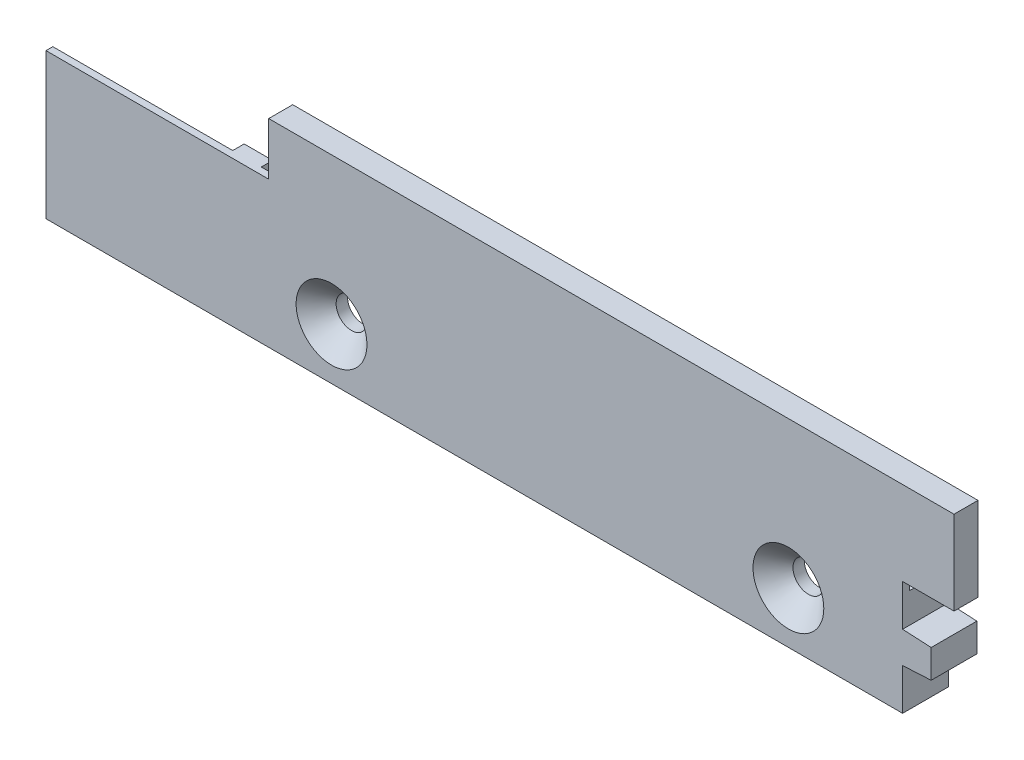
SolidWorks part; units mm, degrees
ref_plane "Front Plane" through (0, 0, 0) normal (0, 0, 1) x (1, 0, 0)
ref_plane "Top Plane" through (0, 0, 0) normal (0, 1, 0) x (1, 0, 0)
ref_plane "Right Plane" through (0, 0, 0) normal (1, 0, 0) x (0, 0, -1)
ref_axis "X-Axis" through (0, 0, 0) along (1, 0, 0)
ref_axis "Y-Axis" through (0, 42.2917, 0) along (0, -1, 0)
ref_axis "Z-Axis" through (0, 0, 55.0015) along (0, 0, -1)
sketch "Sketch1" plane through (0, 0, 0) normal (0, 0, 1) x (1, 0, 0)
  line L1 (-127.8191, -9.8629) -> (22.1809, -9.8629)
  line L2 (22.1809, -9.8629) -> (22.1809, -2.6129)
  line L3 (22.1809, -2.6129) -> (27.1809, -2.6129)
  line L4 (27.1809, -2.6129) -> (27.1809, 2.8871)
  line L5 (27.1809, 2.8871) -> (22.1809, 2.8871)
  line L6 (22.1809, 2.8871) -> (22.1809, 10.1371)
  line L7 (22.1809, 10.1371) -> (31.1809, 10.1371)
  line L8 (31.1809, 10.1371) -> (31.1809, 23.6371)
  line L10 (-127.8191, 15.6371) -> (-127.8191, -9.8629)
  line L12 (-88.8191, -25.8695) -> (-88.8191, 48.9262) construction
  line L13 (31.1809, 13.1371) -> (10.3885, 13.1371) construction
  line L14 (31.1809, 23.6371) -> (-88.8191, 23.6371) construction
  line L15 (-88.8191, 23.6371) -> (-88.8191, 15.6371)
  line L16 (-88.8191, 15.6371) -> (-127.8191, 15.6371)
  line L17 (31.1809, 23.6371) -> (31.1809, 24.8371)
  line L18 (31.1809, 24.8371) -> (-88.8191, 24.8371)
  line L19 (-88.8191, 24.8371) -> (-88.8191, 23.6371)
  point P5 (27.1809, 0.1371)
  dimension "D2" = 10
  dimension "D3" = 20
  dimension "D4" = 5.5
  dimension "D5" = 9
  dimension "D6" = 150
  dimension "D7" = 120
  dimension "D8" = 5
  dimension "D10" = 3
  dimension "D11" = 8
  dimension "D12" = 10.5
  dimension "D13" = 1.2
extrude "Boss-Extrude1" add sketch "Sketch1" along normal blind 8 and the other way blind 8
sketch "Sketch2" plane through (-127.8191, 0, 0) normal (-1, 0, 0) x (0, 0, 1)
  line L0 (-8, -9.8629) -> (8, -9.8629) construction
  line L1 (-6.8, 23.1371) -> (6.8, 23.1371) construction
  line L2 (-6.8, 23.1371) -> (-6.8, 8.1371)
  line L3 (-6.8, 8.1371) -> (6.8, 8.1371)
  line L4 (6.8, 23.1371) -> (6.8, 8.1371)
  line L5 (-8, 24.8371) -> (-8, 15.6371) construction
  line L7 (-8, 2.8871) -> (8, 2.8871) construction
  line L8 (-8, 15.6371) -> (-8, -9.8629) construction
  line L9 (8, 15.6371) -> (8, -9.8629) construction
  line L10 (0, 2.8871) -> (0, 23.1371) construction
  line L11 (-6.8, 23.1371) -> (-3.8, 23.1371)
  line L12 (-3.8, 23.1371) -> (-3.8, 24.8371)
  line L13 (-8, 24.8371) -> (8, 24.8371) construction
  line L14 (-3.8, 24.8371) -> (3.8, 24.8371)
  line L15 (3.8, 24.8371) -> (3.8, 23.1371)
  line L16 (3.8, 23.1371) -> (6.8, 23.1371)
  point P6 (0, 23.1371)
  dimension "D1" = 13.6
  dimension "D2" = 33
  dimension "D3" = 3
  dimension "D4" = 3
  dimension "D6" = 18
  dimension "D7" = 1.2
extrude "Cut-Extrude1" cut sketch "Sketch2" against normal offset from surface (157 mm away) 2 up to face at (31.1809, 17.4871, 0)
sketch "Sketch8" plane through (0, 0, 0) normal (0, 0, 1) x (1, 0, 0)
  line L0 (-127.8191, 15.6371) -> (-127.8191, -9.8629) construction
  line L1 (-107.8191, 24.8371) -> (17.1809, 24.8371)
  line L2 (-107.8191, 24.8371) -> (-107.8191, -9.8629)
  line L3 (-107.8191, -9.8629) -> (17.1809, -9.8629)
  line L4 (17.1809, 24.8371) -> (17.1809, -9.8629)
  line L5 (-127.8191, -9.8629) -> (22.1809, -9.8629) construction
  line L7 (22.1809, 2.8871) -> (22.1809, 10.1371) construction
  line L8 (29.1809, 24.8371) -> (-88.8191, 24.8371) construction
  point P12 (22.1809, 6.5121)
  dimension "D1" = 20
  dimension "D2" = 5
extrude "Cut-Extrude4" cut sketch "Sketch8" against normal blind 2.5 and the other way blind 2.5 contours L2 L3 L4 L1
sketch "Sketch9" plane through (0, 0, 0) normal (0, 0, 1) x (1, 0, 0)
  line L0 (-107.8191, -0.8629) -> (17.1809, -0.8629) construction
  line L1 (-107.8191, 8.1371) -> (-107.8191, -9.8629) construction
  line L2 (17.1809, 8.1371) -> (17.1809, -9.8629) construction
  circle A0 centre (-77.8191, -0.8629) radius 2.7
  circle A1 centre (2.1809, -0.8629) radius 2.7
  dimension "D1" = 5.4
  dimension "D2" = 80
  dimension "D3" = 15
extrude "Cut-Extrude5" cut sketch "Sketch9" against normal through all and the other way through all
chamfer "Chamfer2" distance 5 angle 3 2 edges at (27.1809, -2.6129, 0) (27.1809, 2.8871, 0) first distance on face at (24.6809, -2.6129, 0) first distance on face at (24.6809, 2.8871, 0)
sketch "Sketch14" plane through (0, 8.1371, 0) normal (0, 1, 0) x (1, 0, 0)
  line L0 (-120.3191, 4.5) -> (-115.3191, 4.5)
  line L1 (-115.3191, -4.5) -> (-120.3191, -4.5)
  line L2 (-107.8191, 0) -> (-127.8191, 0) construction
  line L3 (-107.8191, 2.5) -> (-107.8191, -2.5) construction
  line L5 (-127.8191, 6.8) -> (-127.8191, -6.8) construction
  arc A0 (-115.3191, 4.5) -> (-115.3191, -4.5) centre (-115.3191, 0) cw
  arc A1 (-120.3191, -4.5) -> (-120.3191, 4.5) centre (-120.3191, 0) cw
  point P16 (-117.8191, 0)
  dimension "D1" = 4.5
  dimension "D2" = 5
  dimension "D3" = 2.5
extrude "Cut-Extrude8" cut sketch "Sketch14" against normal blind 10
sketch "Sketch15" plane through (0, -1.8629, 0) normal (0, 1, 0) x (1, 0, 0)
  line L7 (-120.3191, -2.6) -> (-115.3191, -2.6)
  line L8 (-115.3191, 2.6) -> (-120.3191, 2.6)
  arc A2 (-120.3191, 4.5) -> (-120.3191, -4.5) centre (-120.3191, 0) ccw construction
  arc A3 (-115.3191, -4.5) -> (-115.3191, 4.5) centre (-115.3191, 0) ccw construction
  arc A6 (-120.3191, 2.6) -> (-120.3191, -2.6) centre (-120.3191, 0) ccw
  arc A7 (-115.3191, -2.6) -> (-115.3191, 2.6) centre (-115.3191, 0) ccw
  dimension "D2" = 2.6
extrude "Cut-Extrude9" cut sketch "Sketch15" against normal through all
sketch "Sketch16" plane through (0, 0, 0) normal (0, 0, 1) x (1, 0, 0)
  line L1 (-137.4451, 59.0989) -> (76.8996, 59.0989)
  line L2 (-137.4451, 59.0989) -> (-137.4451, -25.5467)
  line L3 (-137.4451, -25.5467) -> (76.8996, -25.5467)
  line L4 (76.8996, 59.0989) -> (76.8996, -25.5467)
extrude "Cut-Extrude10" cut sketch "Sketch16" against normal through all
sketch "Sketch17" plane through (0, 0, 0) normal (0, 0, -1) x (-1, 0, 0)
  line L1 (-31.1809, 24.8371) -> (-29.1809, 24.8371)
  line L2 (-31.1809, 24.8371) -> (-31.1809, 10.1371)
  line L3 (-31.1809, 10.1371) -> (-29.1809, 10.1371)
  line L4 (-29.1809, 24.8371) -> (-29.1809, 10.1371)
extrude "Cut-Extrude11" cut sketch "Sketch17" against normal up to surface (3.8 mm away) up to face at (-29.8191, 23.9871, 3.8)
sketch "Sketch18" plane through (0, 0, 0) normal (0, 0, -1) x (-1, 0, 0)
  line L0 (-27.1809, 0.1371) -> (-17.1809, 0.1371) construction
  line L1 (-27.1809, 2.6251) -> (-27.1809, -2.3509) construction
  line L2 (-17.1809, 8.1371) -> (-17.1809, -9.8629) construction
  line L3 (110.3191, -5.8629) -> (125.3191, -5.8629) construction
  line L5 (117.8191, -9.8629) -> (117.8191, -1.8629) construction
  line L9 (120.3191, -1.8629) -> (115.3191, -1.8629) construction
  line L10 (120.3191, -9.8629) -> (115.3191, -9.8629) construction
  circle A0 centre (110.3191, -5.8629) radius 1.35
  circle A1 centre (125.3191, -5.8629) radius 1.35
  circle A2 centre (-22.1809, 0.1371) radius 1.35
  point P17 (117.8191, -5.8629)
  dimension "D2" = 2.7
  dimension "D1" = 15
extrude "Cut-Extrude12" cut sketch "Sketch18" against normal blind 3
chamfer "Chamfer7" distance 3.5 angle 45 2 edges at (4.8809, -0.8629, 8) (-75.1191, -0.8629, 8)
sketch "Sketch19" plane through (0, 0, 6.8) normal (0, 0, -1) x (-1, 0, 0)
  line L0 (-22.1809, 8.1371) -> (127.8191, 8.1371) construction
  line L1 (91.3191, 15.6371) -> (96.3191, 15.6371)
  line L2 (91.3191, 15.6371) -> (91.3191, 8.1371)
  line L3 (91.3191, 8.1371) -> (96.3191, 8.1371)
  line L4 (96.3191, 15.6371) -> (96.3191, 8.1371)
  line L5 (-29.1809, 10.1371) -> (-29.1809, 23.1371) construction
  dimension "D1" = 120.5
  dimension "D2" = 5
extrude "Boss-Extrude2" add sketch "Sketch19" along normal blind 2
equation "\"Largeur Bande\"= 12.3"
equation "\"Largeur Feeder\"= \"Largeur Rail\" + 1.2 + 1.2 + 0.3"
equation "\"Largeur Rail\"= \"Largeur Bande\" + 1"
equation "\"D1@Boss-Extrude1\"=\"Largeur Feeder\"/2"
equation "\"D2@Boss-Extrude1\"=\"Largeur Feeder\"/2"
